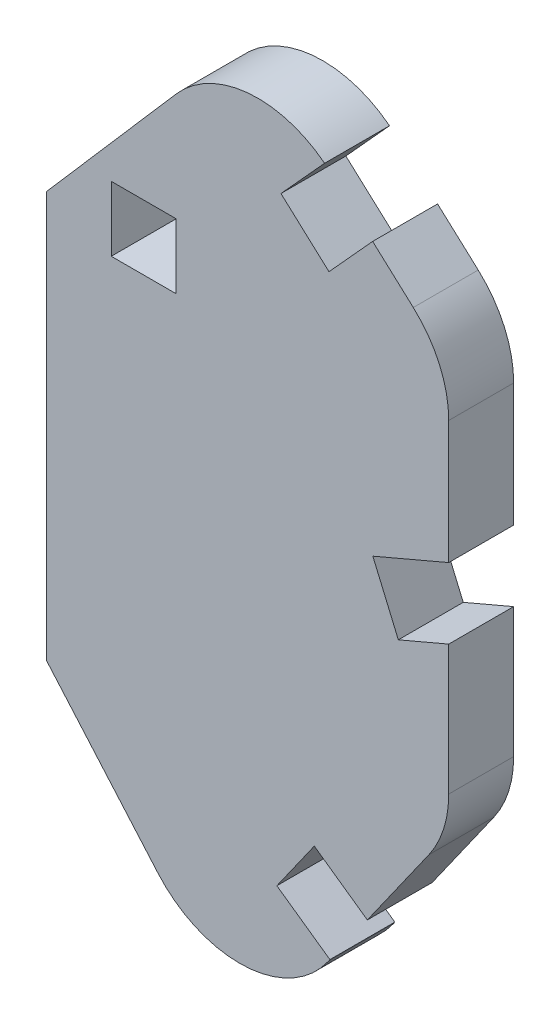
SolidWorks part; units mm, degrees
ref_plane "Front Plane" through (0, 0, 0) normal (0, 0, 1) x (1, 0, 0)
ref_plane "Top Plane" through (0, 0, 0) normal (0, 1, 0) x (1, 0, 0)
ref_plane "Right Plane" through (0, 0, 0) normal (1, 0, 0) x (0, 0, -1)
sketch "Sketch1" plane through (0, 0, 0) normal (0, 0, 1) x (1, 0, 0)
  line L0 (1.524, -10.4973) -> (1.524, -0.9723)
  line L1 (4.572, 0) -> (3.048, 0)
  line L2 (4.572, 0) -> (4.572, -1.524)
  line L3 (4.572, -1.524) -> (3.048, -1.524)
  line L4 (3.048, 0) -> (3.048, -1.524)
  line L5 (1.524, -0.9723) -> (6.2696, 4.4936)
  line L6 (6.2696, 4.4936) -> (8.0555, 2.871)
  line L7 (10.9695, -9.3014) -> (10.9695, -5.4467)
  line L8 (9.0588, -12.0097) -> (10.9695, -9.3014)
  line L9 (6.2696, -15.9632) -> (8.1803, -13.2549)
  line L10 (1.524, -10.4973) -> (6.2696, -15.9632)
  line L11 (1.524, -1.524) -> (1.524, 0) construction
  line L12 (10.9695, -3.7898) -> (10.9695, 0.2236)
  line L13 (9.1835, 1.8462) -> (10.9695, 0.2236)
  line L14 (9.0588, -12.0097) -> (7.8135, -11.1311)
  line L16 (8.0555, 2.871) -> (7.0307, 1.743)
  line L17 (8.1803, -13.2549) -> (6.935, -12.3764)
  line L19 (9.1835, 1.8462) -> (8.1587, 0.7182)
  line L20 (10.9695, -3.7898) -> (9.1882, -4.5498)
  line L21 (7.8135, -11.1311) -> (6.935, -12.3764)
  line L22 (9.1882, -4.5498) -> (9.7863, -5.9516)
  line L24 (9.7863, -5.9516) -> (10.9695, -5.4467)
  line L25 (7.0307, 1.743) -> (8.1587, 0.7182)
  dimension "D1" = 6.35
  dimension "D2" = 9.525
  dimension "D3" = 0
  dimension "D4" = 9.525
  dimension "D5" = 1.524
extrude "Boss-Extrude1" add sketch "Sketch1" along normal blind 1.524
fillet "Fillet1" radius 2.54 4 edges at (6.2696, -15.9632, 0.762) (10.9695, -9.3014, 0.762) (6.2696, 4.4936, 0.762) (10.9695, 0.2236, 0.762)
